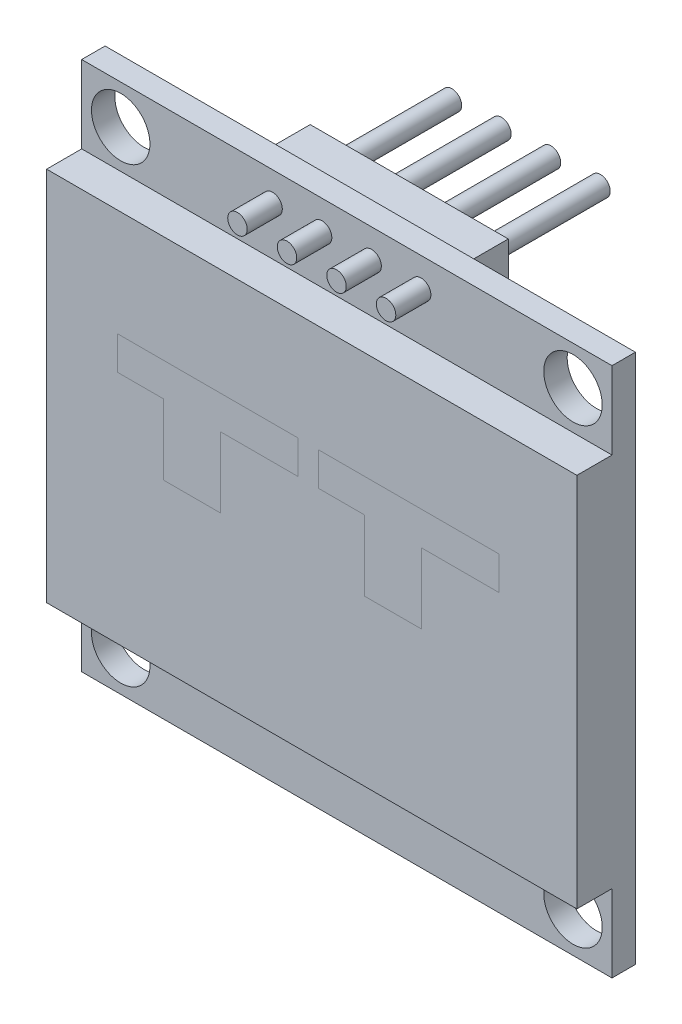
SolidWorks part; units mm, degrees
ref_plane "Спереди" through (0, 0, 0) normal (0, 0, 1) x (1, 0, 0)
ref_plane "Сверху" through (0, 0, 0) normal (0, 1, 0) x (1, 0, 0)
ref_plane "Справа" through (0, 0, 0) normal (1, 0, 0) x (0, 0, -1)
sketch "Эскиз1" plane through (0, 0, 0) normal (0, 0, 1) x (1, 0, 0)
  line L1 (-13.6, -13.6) -> (13.6, -13.6)
  line L2 (-13.6, -13.6) -> (-13.6, 13.6)
  line L3 (-13.6, 13.6) -> (13.6, 13.6)
  line L4 (13.6, -13.6) -> (13.6, 13.6)
  line L5 (-13.6, -13.6) -> (13.6, 13.6) construction
  line L6 (-13.6, 13.6) -> (13.6, -13.6) construction
  point P0 (0, 0)
  dimension "D1" = 27.2
  dimension "D2" = 27.2
extrude "плата" add sketch "Эскиз1" along normal blind 1.2
sketch "Эскиз2" plane through (0, 0, 1.2) normal (0, 0, 1) x (1, 0, 0)
  line L0 (13.6, -13.6) -> (13.6, 13.6) construction
  line L1 (-13.6, -9.63) -> (13.6, -9.63)
  line L2 (-13.6, -9.63) -> (-13.6, 9.63)
  line L3 (-13.6, 9.63) -> (13.6, 9.63)
  line L4 (13.6, -9.63) -> (13.6, 9.63)
  line L5 (-13.6, -9.63) -> (13.6, 9.63) construction
  line L6 (-13.6, 9.63) -> (13.6, -9.63) construction
  point P0 (0, 0)
  dimension "D1" = 19.26
extrude "экран" add sketch "Эскиз2" along normal blind 1.8
sketch "Эскиз3" plane through (0, 0, 1.2) normal (0, 0, 1) x (1, 0, 0)
  line L0 (-3.81, 12.1) -> (-1.27, 12.1) construction
  line L1 (-1.27, 12.1) -> (1.27, 12.1) construction
  line L2 (1.27, 12.1) -> (3.81, 12.1) construction
  line L3 (-13.6, 13.6) -> (-13.6, 9.63) construction
  line L4 (13.6, 13.6) -> (-13.6, 13.6) construction
  circle A0 centre (-3.81, 12.1) radius 0.5
  circle A1 centre (-1.27, 12.1) radius 0.5
  circle A2 centre (1.27, 12.1) radius 0.5
  circle A3 centre (3.81, 12.1) radius 0.5
  dimension "D2" = 1
  dimension "D1" = 2.54
  dimension "D3" = 9.79
  dimension "D4" = 1.5
extrude "обратная сторона пинов" add sketch "Эскиз3" along normal up to surface (1.8 mm away) and the other way blind 9.2 up to face at (0, 0, 3)
sketch "Эскиз4" plane through (0, 0, 1.2) normal (0, 0, 1) x (1, 0, 0)
  line L0 (-13.6, 13.6) -> (-13.6, 9.63) construction
  line L1 (11.6, -11.6) -> (-11.6, -11.6) construction
  line L2 (11.6, -11.6) -> (11.6, 11.6) construction
  line L3 (11.6, 11.6) -> (-11.6, 11.6) construction
  line L4 (-11.6, -11.6) -> (-11.6, 11.6) construction
  line L5 (11.6, -11.6) -> (-11.6, 11.6) construction
  line L6 (11.6, 11.6) -> (-11.6, -11.6) construction
  line L7 (13.6, 13.6) -> (-13.6, 13.6) construction
  circle A0 centre (-11.6, 11.6) radius 1.5
  circle A1 centre (11.6, 11.6) radius 1.5
  circle A2 centre (11.6, -11.6) radius 1.5
  circle A3 centre (-11.6, -11.6) radius 1.5
  point P0 (0, 0)
  dimension "D1" = 3
  dimension "D2" = 2
  dimension "D3" = 2
extrude "крепежные отверстия" cut sketch "Эскиз4" against normal through all
sketch "Эскиз5" plane through (0, 0, 0) normal (0, 0, -1) x (-1, 0, 0)
  line L0 (-3.81, 12.1) -> (3.81, 12.1) construction
  line L1 (-5.08, 10.83) -> (5.08, 10.83)
  line L2 (-5.08, 10.83) -> (-5.08, 13.37)
  line L3 (-5.08, 13.37) -> (5.08, 13.37)
  line L4 (5.08, 10.83) -> (5.08, 13.37)
  line L5 (-5.08, 10.83) -> (5.08, 13.37) construction
  point P6 (0, 12.1)
  point P7 (0, 12.1)
  dimension "D1" = 2.54
  dimension "D2" = 10.16
extrude "основание разъема" add sketch "Эскиз5" along normal blind 2
sketch "Эскиз6" plane through (0, 0, 3) normal (0, 0, 1) x (1, 0, 0)
  line L0 (-9.9684, 4.1368) -> (-9.9684, 2.4238)
  line L1 (-9.9684, 2.4238) -> (-7.5993, 2.4238)
  line L2 (-7.5993, 2.4238) -> (-7.5993, -1.1845)
  line L3 (-7.5993, -1.1845) -> (-4.6835, -1.1845)
  line L4 (-4.6835, -1.1845) -> (-4.6835, 2.4238)
  line L5 (-4.6835, 2.4238) -> (-0.7107, 2.4238)
  line L6 (-0.7107, 2.4238) -> (-0.7107, 4.1368)
  line L7 (-0.7107, 4.1368) -> (-9.9684, 4.1368)
  line L8 (0.3463, 4.1368) -> (0.3463, 2.4238)
  line L9 (0.3463, 2.4238) -> (2.7153, 2.4238)
  line L10 (2.7153, 2.4238) -> (2.7153, -1.1845)
  line L11 (2.7153, -1.1845) -> (5.6312, -1.1845)
  line L12 (5.6312, -1.1845) -> (5.6312, 2.4238)
  line L13 (5.6312, 2.4238) -> (9.604, 2.4238)
  line L14 (9.604, 2.4238) -> (9.604, 4.1368)
  line L15 (9.604, 4.1368) -> (0.3463, 4.1368)
split line "Разделяющая линия2"
